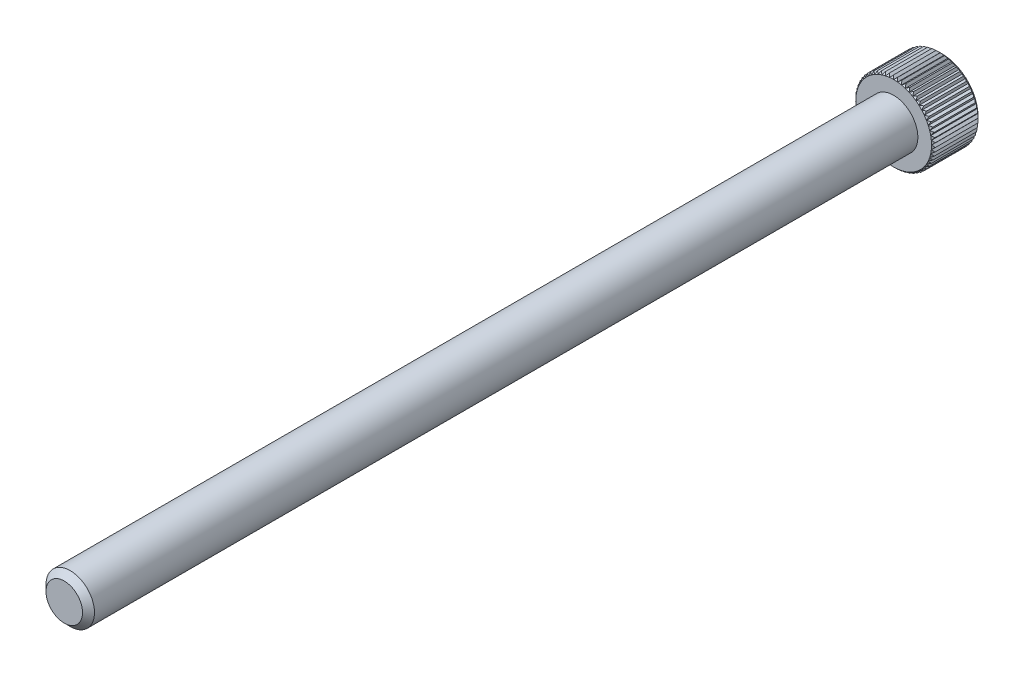
SolidWorks part; units mm, degrees
ref_plane "Front Plane" through (0, 0, 0) normal (0, 0, 1) x (1, 0, 0)
ref_plane "Top Plane" through (0, 0, 0) normal (0, 1, 0) x (1, 0, 0)
ref_plane "Right Plane" through (0, 0, 0) normal (1, 0, 0) x (0, 0, -1)
sketch "Sketch0" plane through (0, 0, 0) normal (1, 0, 0) x (0, 0, -1)
  line L0 (0, 0) -> (82.55, 0) construction
  line L1 (0, -2.413) -> (0, 2.413) construction
  line L2 (87.376, -3.9688) -> (87.376, 3.9687) construction
  line L3 (87.376, -1.9844) -> (87.376, 1.9844) construction
  point P2 (87.376, 0)
  point P4 (22.225, 0)
  point P8 (0, 0)
  point P11 (87.376, 0)
  point P14 (87.376, 0)
  dimension "Min Thread" = 22.225
  dimension "OD" = 4.826
  dimension "screw length" = 82.55
  dimension "head depth" = 4.826
  dimension "head dia" = 7.9375
  dimension "hex dia" = 3.9688
sketch "Sketch1" plane through (0, 0, 0) normal (0, 0, 1) x (1, 0, 0)
  circle A0 centre (0, 0) radius 2.413
  dimension "OD" = 4.826
extrude "Extrude1" add sketch "Sketch1" against normal blind 82.55
sketch "Sketch2" [suppressed] plane through (0, 0, 0) normal (0, 0, 1) x (1, 0, 0)
  circle A0 centre (0, 0) radius 2.413 construction
  circle A1 centre (0, 0) radius 2.413
chamfer "Chamfer3" distance 0.5953 angle 45 1 edges at (2.413, 0, 0)
sketch "Sketch3" [suppressed] plane through (0, 0, 0) normal (1, 0, 0) x (0, 0, -1)
  line L0 (-0.6945, 2.413) -> (-0.3969, 1.8974)
  line L1 (-0.3969, 1.8974) -> (-0.2977, 1.8974)
  line L2 (-0.2977, 1.8974) -> (0, 2.413)
  line L3 (-0.6945, 2.413) -> (0, 2.413)
  line L4 (-0.3473, 2.413) -> (-0.3473, 1.8974) construction
  line L5 (-0.5457, 2.1552) -> (-0.1488, 2.1552) construction
  line L6 (0, 2.413) -> (0, -2.413) construction
  dimension "D1" = 0.0992
  dimension "D2" = 0.3969
  dimension "D3" = 60
sketch "Sketch6" plane through (0, 0, -82.55) normal (0, 0, -1) x (-1, 0, 0)
  circle A0 centre (0, 0) radius 3.9688
  dimension "head dia" = 7.9375
extrude "Extrude2" add sketch "Sketch6" along normal blind 4.826
sketch "Sketch7" plane through (0, 0, -87.376) normal (0, 0, -1) x (-1, 0, 0)
  line L1 (0, 2.2914) -> (-1.9844, 1.1457)
  line L2 (-1.9844, 1.1457) -> (-1.9844, -1.1457)
  line L3 (-1.9844, -1.1457) -> (0, -2.2914)
  line L4 (0, -2.2914) -> (1.9844, -1.1457)
  line L5 (1.9844, -1.1457) -> (1.9844, 1.1457)
  line L6 (1.9844, 1.1457) -> (0, 2.2914)
  circle A0 centre (0, 0) radius 1.9844 construction
  dimension "hex dia" = 3.9688
extrude "Cut-Extrude1" cut sketch "Sketch7" against normal blind 2.9766
sketch "Sketch8" plane through (0, 0, -87.376) normal (0, 0, -1) x (-1, 0, 0)
  circle A0 centre (0, 0) radius 2.2914
extrude "Cut-Extrude2" cut sketch "Sketch8" against normal through all draft 45
chamfer "Chamfer1" distance 0.3969 angle 45 1 edges at (-3.9688, 0, -87.376)
chamfer "Chamfer2" distance 0.1984 angle 45 1 edges at (-3.9688, 0, -82.55)
sketch "Sketch9" plane through (0, 0, 0) normal (1, 0, 0) x (0, 0, -1)
  line L0 (87.376, -3.9688) -> (87.376, 3.9688) construction
  line L2 (82.55, -3.9688) -> (82.55, 3.9687) construction
  line L9 (86.9791, 3.9688) -> (82.7484, 3.9688) construction
  line L10 (0, -2.413) -> (0, 2.413) construction
  line L11 (0, -2.413) -> (0, 2.413)
  line L12 (1.9844, -2.413) -> (1.9844, 2.413) construction
  point P4 (87.376, 0)
  point P6 (82.55, 0)
  point P14 (1.9844, 0)
  point P15 (1.9844, -2.413)
  dimension "D1" = 1.9844
ref_plane "Contact Plane 1" through (0, 0, -82.55) normal (0, 0, 1) x (1, 0, 0)
ref_axis "Center Axis 1" through (0, 0, 9.7485) along (0, 0, -1)
curve "Helix/Spiral1" [suppressed] pitch 0.7937 height 83.3438 turns 105 parameters "pitch"=0.7937
sweep "Cut-Sweep1" [suppressed] cut profiles "Sketch3" path "Helix/Spiral1"
sketch "Sketch5" [suppressed] plane through (0, 0, 0) normal (1, 0, 0) x (0, 0, -1)
  line L1 (82.5754, 2.413) -> (22.225, 2.413)
  line L2 (82.5754, 2.413) -> (82.5754, 0)
  line L3 (82.5754, 0) -> (21.3467, 0)
  line L4 (0, 0) -> (82.55, 0) construction
  line L5 (22.225, 2.413) -> (21.3467, 0)
  line L6 (0, 0) -> (87.376, 0) construction
  dimension "D1" = 70
  dimension "D3" = 4.8006
revolve "partially thread" [suppressed] add sketch "Sketch5" angle 360 about L6
sketch "Sketch10" plane through (0, 0, -82.55) normal (0, 0, 1) x (1, 0, 0)
  line L0 (-0.4271, 4.1672) -> (0, 3.7703)
  line L1 (0, 3.7703) -> (0.4271, 4.1672)
  line L2 (0, 3.7703) -> (0, 4.1672) construction
  line L3 (-0.4271, 4.1672) -> (0.4271, 4.1672)
  line L4 (0, -4.3596) -> (0, 4.3596) construction
  line L5 (0, 0) -> (0.2077, 3.9633) construction
  line L6 (-0.2077, 3.9633) -> (0, 0) construction
  circle A2 centre (0, 0) radius 3.9688 construction
  circle A5 centre (0, 0) radius 3.7703 construction
  dimension "D2" = 0.3969
  dimension "D1" = 6
extrude "Cut-Extrude3" cut sketch "Sketch10" against normal through all
pattern_circular "CirPattern1" count 60 over 360 about axis through (0, 0, -87.376) along (0, 0, 1) of "Cut-Extrude3"
equation "\"D3@Helix/Spiral1\"=\"pitch@Helix/Spiral1\"+\"screw length@Sketch0\""
equation "\"D1@Sketch3\" = \"pitch@Helix/Spiral1\"*.125"
equation "\"D2@Sketch3\" = \"pitch@Helix/Spiral1\"*.5"
equation "\"D1@Cut-Extrude1\"=\"hex dia@Sketch0\"*.75"
equation "\"D1@Chamfer1\"=\"head dia@Sketch0\"*.05"
equation "\"D1@Chamfer2\" = \"D1@Chamfer1\"/2"
equation "\"D1@Chamfer3\" = \"pitch@Helix/Spiral1\"*.750"
equation "\"D2@Sketch10\"=\"D1@Chamfer1\""
equation "\"D1@CirPattern1\"=\"D3@CirPattern1\"/\"D1@Sketch10\""
equation "\"D1@Sketch9\"=\"pitch@Helix/Spiral1\"*2.5"
equation "\"OD@Sketch1\"=\"OD@Sketch0\""
equation "\"screw length@Extrude1\"=\"screw length@Sketch0\""
equation "\"head depth@Extrude2\"=\"head depth@Sketch0\""
equation "\"head dia@Sketch6\"=\"head dia@Sketch0\""
equation "\"hex dia@Sketch7\"=\"hex dia@Sketch0\""
equation "\"D3@Sketch5\"=\"head depth@Sketch0\"-.001"
